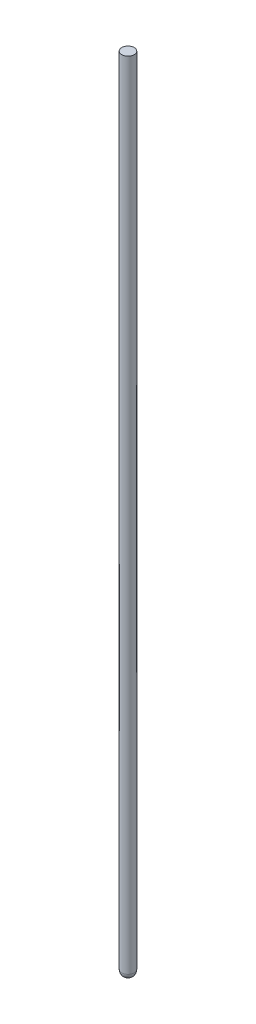
SolidWorks part; units mm, degrees
ref_plane "Front Plane" through (0, 0, 0) normal (0, 0, 1) x (1, 0, 0)
ref_plane "Top Plane" through (0, 0, 0) normal (0, 1, 0) x (1, 0, 0)
ref_plane "Right Plane" through (0, 0, 0) normal (1, 0, 0) x (0, 0, -1)
sketch "Sketch1" plane through (0, 0, 0) normal (0, 1, 0) x (1, 0, 0)
  circle A0 centre (0, 0) radius 0.1984
  dimension "D1" = 0.3969
extrude "Boss-Extrude1" add sketch "Sketch1" along normal blind 25.4
dome "Dome1" faces to dome 1 distance 0.1984 reverse direction no elliptical dome no face at (0, 0, 0.1984) parameters "D1"=0.1984
